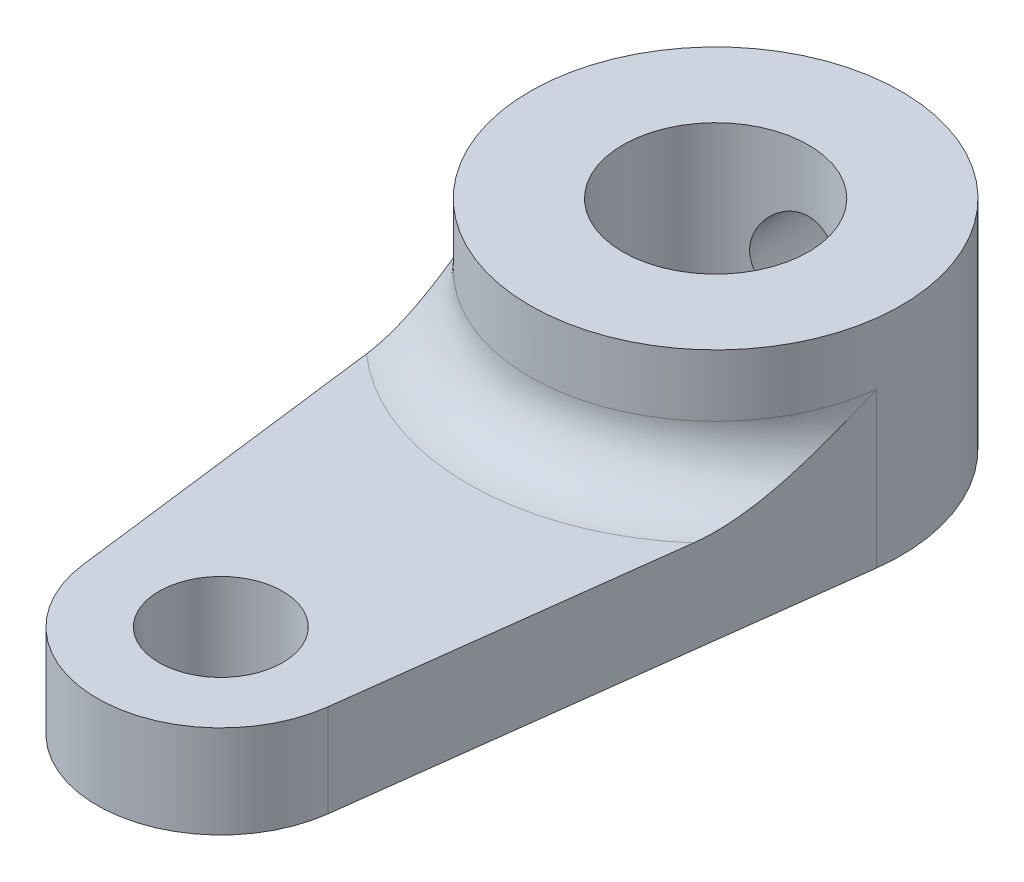
SolidWorks part; units mm, degrees
ref_plane "Front Plane" through (0, 0, 0) normal (0, 0, 1) x (1, 0, 0)
ref_plane "Top Plane" through (0, 0, 0) normal (0, 1, 0) x (1, 0, 0)
ref_plane "Right Plane" through (0, 0, 0) normal (1, 0, 0) x (0, 0, -1)
sketch "Sketch2" plane through (0, 0, 0) normal (0, 1, 0) x (1, 0, 0)
  line L0 (5.9529, 15.25) -> (3.9686, -0.5)
  line L1 (-5.9529, 15.25) -> (-3.9686, -0.5)
  arc A0 (-3.9686, -0.5) -> (3.9686, -0.5) centre (0, 0) ccw
  arc A1 (5.9529, 15.25) -> (-5.9529, 15.25) centre (0, 16) ccw
  circle A2 centre (0, 0) radius 2
  dimension "D1" = 8
  dimension "D3" = 4
  dimension "D4" = 6
  dimension "D2" = 16
extrude "Boss-Extrude1" add sketch "Sketch2" along normal blind 3
sketch "Sketch4" plane through (0, 3, 0) normal (0, 1, 0) x (1, 0, 0)
  circle A0 centre (0, 16) radius 3
  circle A1 centre (0, 16) radius 6
  dimension "D1" = 6
extrude "Boss-Extrude2" add sketch "Sketch4" along normal blind 4
sketch "Sketch5" plane through (0, 3, 0) normal (0, 1, 0) x (1, 0, 0)
  circle A1 centre (0, 16) radius 3
  circle A2 centre (0, 16) radius 3
  dimension "D1" = 0
extrude "Cut-Extrude1" cut sketch "Sketch5" against normal blind 18
sketch "Sketch6" plane through (0, 0, 0) normal (0, 0, 1) x (1, 0, 0)
  line L2 (-3.9686, 0) -> (3.9686, 0) construction
  circle A0 centre (0, 3.5) radius 1.5
  dimension "D1" = 3.5
  dimension "D2" = 3
extrude "Cut-Extrude2" cut sketch "Sketch6" against normal blind 28 from offset 17 offset against normal yes
fillet "Fillet1" radius 2 1 edges at (0, 3, -10)
